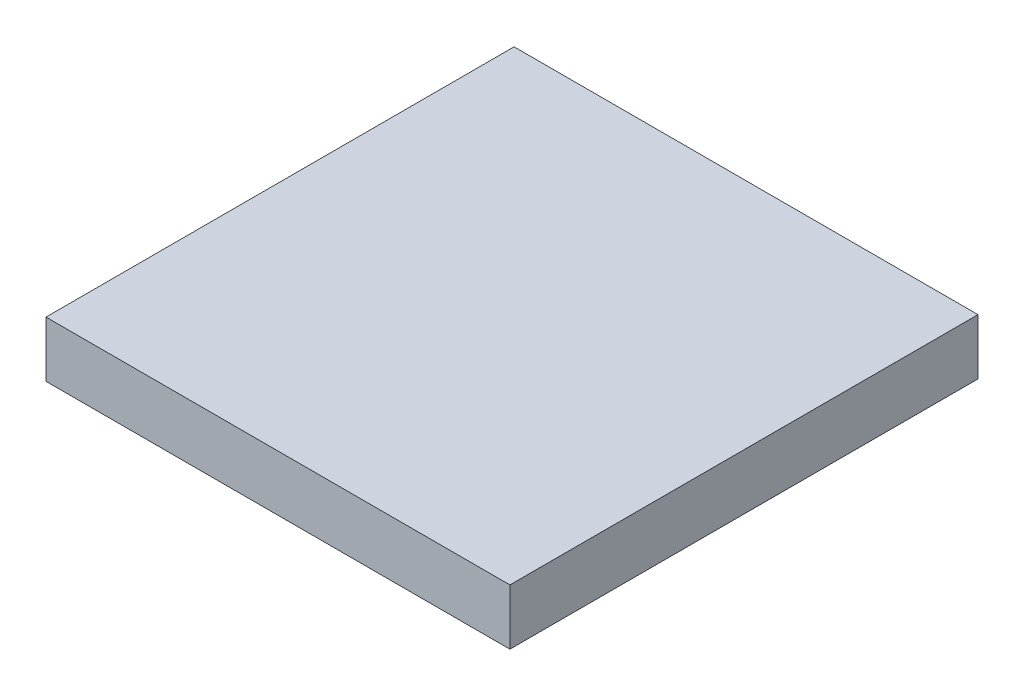
SolidWorks part; units mm, degrees
ref_plane "前视基准面" through (0, 0, 0) normal (0, 0, 1) x (1, 0, 0)
ref_plane "上视基准面" through (0, 0, 0) normal (0, 1, 0) x (1, 0, 0)
ref_plane "右视基准面" through (0, 0, 0) normal (1, 0, 0) x (0, 0, -1)
sketch "草图1" plane through (0, 0, 0) normal (0, 1, 0) x (1, 0, 0)
  line L0 (0, 0) -> (7.5, 0) construction
  line L2 (20, -20) -> (-5, -20)
  line L3 (20, -20) -> (20, 5.2265)
  line L4 (20, 5.2265) -> (-5, 5.2265)
  line L5 (-5, -20) -> (-5, 5.2265)
  line L6 (20, -20) -> (-5, 5.2265) construction
  line L7 (20, 5.2265) -> (-5, -20) construction
  circle A0 centre (0, 0) radius 2.5
  circle A1 centre (0, 0) radius 1.5
  circle A2 centre (7.5, 0) radius 2.5
  circle A3 centre (7.5, 0) radius 1.5
  circle A4 centre (15, 0) radius 2.5
  circle A5 centre (15, 0) radius 1.5
  circle A6 centre (7.5, -7.3867) radius 2.5
  circle A7 centre (7.5, -7.3867) radius 1.5
  circle A8 centre (15, -7.3867) radius 2.5
  circle A9 centre (15, -7.3867) radius 1.5
  circle A10 centre (7.5, -14.7735) radius 2.5
  circle A11 centre (7.5, -14.7735) radius 1.5
  circle A12 centre (15, -14.7735) radius 2.5
  circle A13 centre (15, -14.7735) radius 1.5
  circle A14 centre (0, -7.3867) radius 2.5
  circle A15 centre (0, -7.3867) radius 1.5
  circle A16 centre (0, -14.7735) radius 2.5
  circle A17 centre (0, -14.7735) radius 1.5
  dimension "D1" = 3
  dimension "D2" = 5
  dimension "D5" = 7.5
  dimension "D3" = 3
  dimension "D4" = 3
extrude "凸台-拉伸1" add sketch "草图1" along normal blind 3 contours L5 L4 L3 L2
extrude "切除-拉伸1" cut sketch "草图1<3>" along normal blind 2 contours A12
sketch "草图1<3>" plane through (0, 0, 0) normal (0, 1, 0) x (1, 0, 0) same geometry as "草图1"
pattern_linear "阵列(线性)1" count 3 spacing 7.5 along (0, 0, -1) count 3 spacing 7.5 along (-1, 0, 0) of "切除-拉伸1"
extrude "切除-拉伸2" cut sketch "草图1<4>" along normal blind 2.5 contours A13
sketch "草图1<4>" plane through (0, 0, 0) normal (0, 1, 0) x (1, 0, 0) same geometry as "草图1"
pattern_linear "阵列(线性)2" count 3 spacing 7.5 along (0, 0, -1) count 3 spacing 7.5 along (-1, 0, 0) of "切除-拉伸2"
